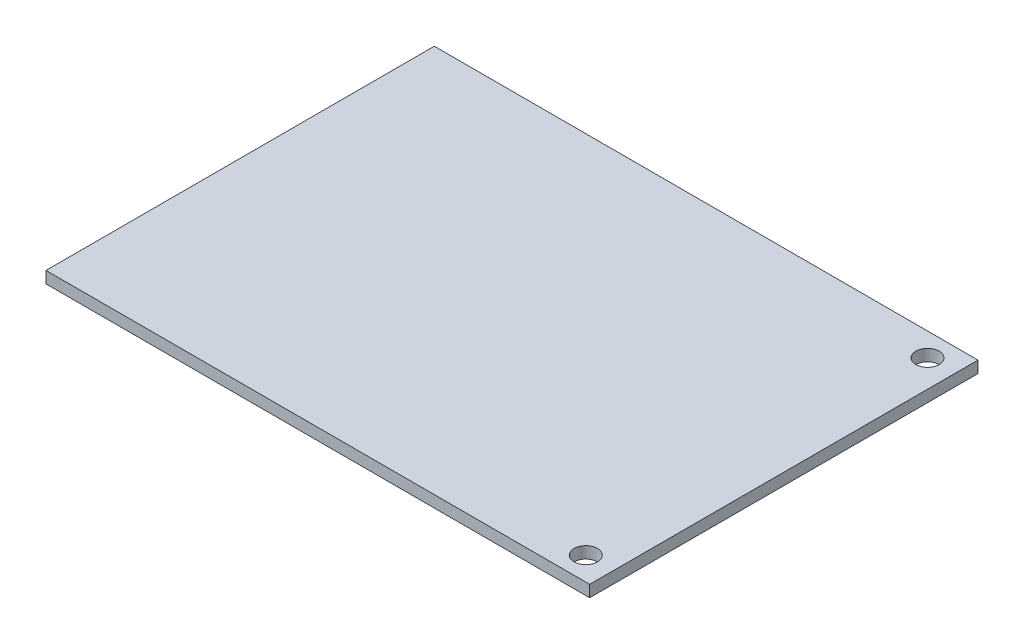
SolidWorks part; units mm, degrees
ref_plane "Front Plane" through (0, 0, 0) normal (0, 0, 1) x (1, 0, 0)
ref_plane "Top Plane" through (0, 0, 0) normal (0, 1, 0) x (1, 0, 0)
ref_plane "Right Plane" through (0, 0, 0) normal (1, 0, 0) x (0, 0, -1)
sketch "Sketch1" plane through (0, 0, 0) normal (0, 1, 0) x (1, 0, 0)
  line L1 (0, 0) -> (70, 0)
  line L2 (0, 0) -> (0, 50)
  line L3 (0, 50) -> (70, 50)
  line L4 (70, 0) -> (70, 50)
  circle A0 centre (66.5, 47) radius 1.5
  circle A1 centre (66.5, 3) radius 1.5
  dimension "D1" = 3
  dimension "D2" = 3.5
  dimension "D3" = 3
  dimension "D4" = 3
  dimension "D5" = 50
  dimension "D6" = 70
extrude "Boss-Extrude1" add sketch "Sketch1" along normal blind 1.5
